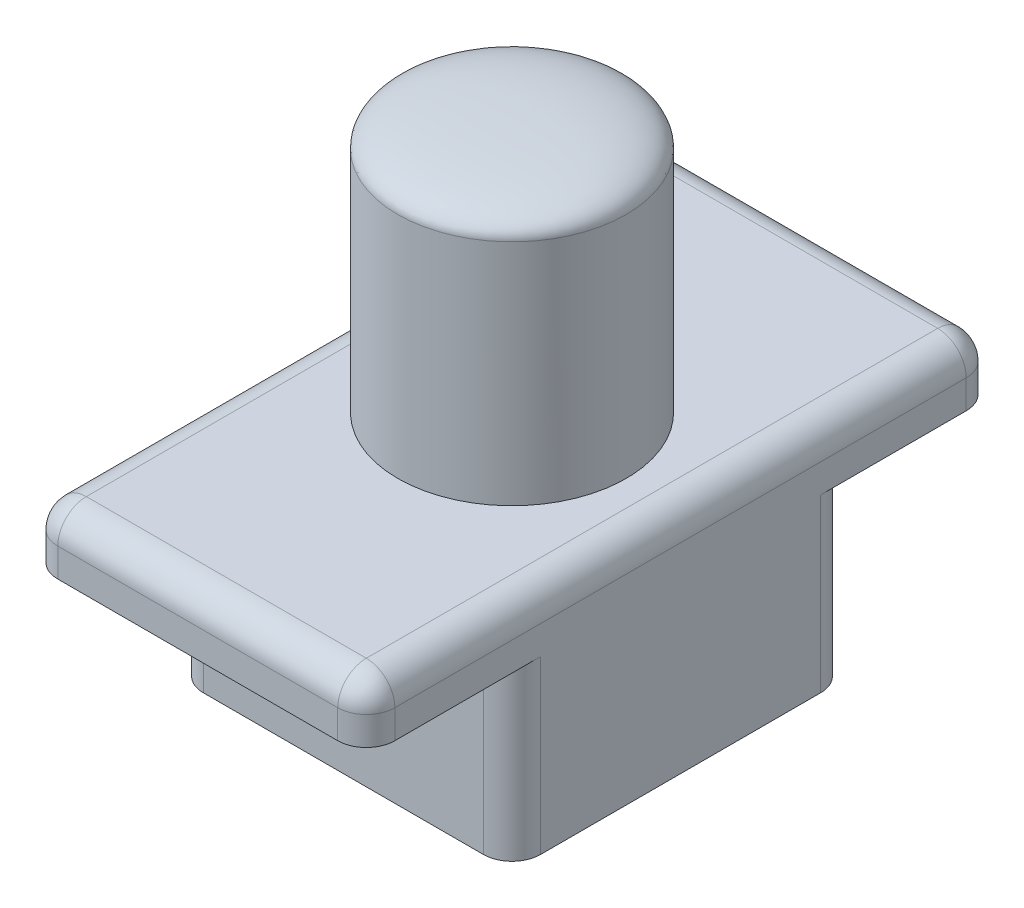
SolidWorks part; units mm, degrees
material "ABS PC"
ref_plane "Front Plane" through (0, 0, 0) normal (0, 0, 1) x (1, 0, 0)
ref_plane "Top Plane" through (0, 0, 0) normal (0, 1, 0) x (1, 0, 0)
ref_plane "Right Plane" through (0, 0, 0) normal (1, 0, 0) x (0, 0, -1)
sketch "Sketch1" plane through (0, 0, 0) normal (1, 0, 0) x (0, 0, -1)
  line L0 (-5.5, 4) -> (5.5, 4)
  line L1 (-2.95, 0) -> (-2.95, 3)
  line L2 (-2.95, 3) -> (-5.5, 3)
  line L3 (0, 4) -> (0, 0) construction
  line L4 (2.95, 0) -> (-2.95, 0)
  line L5 (2.95, 0) -> (2.95, 3)
  line L6 (0, 4) -> (0, 0) construction
  line L7 (-5.5, 3) -> (-5.5, 4)
  line L8 (2.95, 3) -> (5.5, 3)
  line L9 (5.5, 3) -> (5.5, 4)
  dimension "D1" = 4
  dimension "D2" = 2.95
  dimension "D3" = 3
  dimension "D4" = 2.55
extrude "Extrude1" add sketch "Sketch1" along normal mid plane 5.9
sketch "Sketch2" plane through (0, 4, 0) normal (0, 1, 0) x (1, 0, 0)
  circle A0 centre (0, 0) radius 2
  dimension "D1" = 4
extrude "Extrude2" add sketch "Sketch2" along normal blind 4
sketch "Sketch3" plane through (0, 0, 0) normal (0, 0, 1) x (1, 0, 0)
  line L0 (0, 8) -> (2, 8)
  line L1 (0, 8) -> (0, 8.5)
  line L2 (2, 8) -> (-2, 8) construction
  line L3 (2, 8) -> (-2, 8) construction
  spline S1 degree 3 poles (0, 8.5) (0.2102, 8.5) (0.5195, 8.494) (0.9136, 8.4676) (1.1973, 8.4359) (1.4649, 8.3882) (1.6687, 8.3293) (1.8125, 8.2628) (1.9067, 8.1994) (1.9758, 8.1184) (2.0004, 8.0454) (2, 8) knots 0 0 0 0 0.25 0.375 0.5 0.625 0.75 0.8125 0.875 0.9375 0.990999 0.990999 0.990999 0.990999
  dimension "D2" = 0.5
revolve "Revolve1" add sketch "Sketch3" angle 360 about L1
fillet "Fillet1" radius 0.5 12 edges at (0, 4, 5.5) (-2.95, 4, 0) (0, 4, -5.5) (2.95, 4, 0) (-2.95, 1.5, 2.95) (-2.95, 1.5, -2.95) (2.95, 1.5, -2.95) (2.95, 1.5, 2.95) (2.95, 3.5, 5.5) (-2.95, 3.5, 5.5) (-2.95, 3.5, -5.5) (2.95, 3.5, -5.5)
sketch "Sketch4" plane through (0, 0, 0) normal (0, -1, 0) x (1, 0, 0)
  line L2 (1.9989, 2.45) -> (1.9989, -2.45)
  line L3 (1.9989, 1.9989) -> (1.9989, -1.9989)
  line L5 (2.45, -1.9989) -> (-2.45, -1.9989)
  line L6 (1.9989, -1.9989) -> (-1.9989, -1.9989)
  line L8 (-1.9989, 2.45) -> (-1.9989, -2.45)
  line L9 (-1.9989, 1.9989) -> (-1.9989, -1.9989)
  line L11 (2.45, 1.9989) -> (-2.45, 1.9989)
  line L12 (1.9989, 1.9989) -> (-1.9989, 1.9989)
  dimension "D1" = 0.9511
  dimension "D2" = 0.9511
  dimension "D3" = 0.9511
  dimension "D4" = 0.9511
extrude "Cut-Extrude1" cut sketch "Sketch4" against normal blind 2.8
sketch "Sketch5" plane through (0, 2.8, 0) normal (0, -1, 0) x (1, 0, 0)
  circle A0 centre (0, 0) radius 0.75
  dimension "D1" = 1.5
extrude "Cut-Extrude2" cut sketch "Sketch5" against normal blind 0.2
